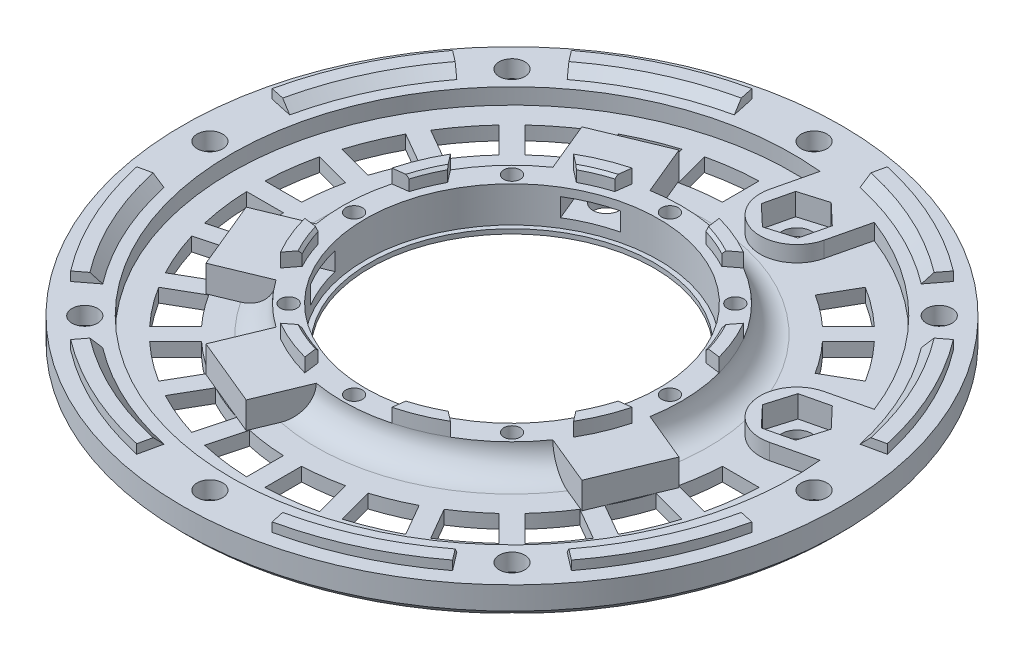
SolidWorks part; units mm, degrees
ref_plane "Front Plane" through (0, 0, 0) normal (0, 0, 1) x (1, 0, 0)
ref_plane "Top Plane" through (0, 0, 0) normal (0, 1, 0) x (1, 0, 0)
ref_plane "Right Plane" through (0, 0, 0) normal (1, 0, 0) x (0, 0, -1)
sketch "Sketch1" plane through (0, 0, 0) normal (0, 1, 0) x (1, 0, 0)
  circle A0 centre (0, 0) radius 16.025
  circle A1 centre (0, 0) radius 36
  dimension "D1" = 32.05
  dimension "D2" = 72
extrude "Boss-Extrude1" add sketch "Sketch1" along normal blind 1
sketch "Sketch2" plane through (0, 0, 0) normal (0, -1, 0) x (1, 0, 0)
  circle A0 centre (0, 0) radius 17.25 construction
  circle A1 centre (0, 0) radius 18.5 construction
  circle A2 centre (0, 0) radius 18.5
  circle A3 centre (0, 0) radius 16.025 construction
  circle A4 centre (0, 0) radius 16.025
  arc A5 (-1.2, 18.461) -> (-4.705, 17.8917) centre (0, 0) ccw construction
  point P3 (0, -17.25)
extrude "Boss-Extrude2" add sketch "Sketch2" against normal offset from surface (3.9 mm away) 3.9 up to face at (0, 0, 36)
fillet "Fillet1" radius 2.9 1 edges at (0, 1, 18.5)
sketch "Sketch4" plane through (0, 0, 0) normal (0, 1, 0) x (1, 0, 0)
  circle A0 centre (0, 0) radius 15.525
  circle A1 centre (0, 0) radius 36
  circle A2 centre (0, 0) radius 36
  circle A3 centre (0, 0) radius 16.025 construction
  dimension "D2" = 0.5
  dimension "D1" = 0
extrude "Boss-Extrude3" add sketch "Sketch4" against normal blind 0.5
sketch "Sketch5" plane through (0, 1, 0) normal (0, 1, 0) x (1, 0, 0)
  line L0 (27.99, -0.75) -> (19.9859, -0.75) construction
  line L1 (19.9859, 0.75) -> (27.99, 0.75) construction
  line L2 (27.99, -0.75) -> (19.9859, -0.75) construction
  line L3 (19.9859, 0.75) -> (27.99, 0.75) construction
  line L4 (0, 0) -> (36, 0) construction
  line L5 (0, 0) -> (34.7733, 9.3175) construction
  line L6 (34.7733, 9.3175) -> (36, 0) construction
  line L7 (0, 0) -> (35.3867, 4.6587) construction
  line L8 (27.99, 1) -> (23.9792, 1)
  line L9 (27.295, 6.2784) -> (23.4209, 5.2403)
  line L10 (27.99, -1) -> (23.9792, -1)
  line L11 (27.295, -6.2784) -> (23.4209, -5.2403)
  line L12 (26.7774, -8.2103) -> (22.9033, -7.1722)
  line L13 (24.74, -13.129) -> (21.2666, -11.1236)
  line L14 (23.74, -14.861) -> (20.2666, -12.8556)
  line L15 (20.499, -19.0848) -> (17.6629, -16.2487)
  line L16 (19.0848, -20.499) -> (16.2487, -17.6629)
  line L17 (14.861, -23.74) -> (12.8556, -20.2666)
  line L18 (13.129, -24.74) -> (11.1236, -21.2666)
  line L19 (8.2103, -26.7774) -> (7.1722, -22.9033)
  line L20 (6.2784, -27.295) -> (5.2403, -23.4209)
  line L21 (1, -27.99) -> (1, -23.9792)
  line L22 (-1, -27.99) -> (-1, -23.9792)
  line L23 (-6.2784, -27.295) -> (-5.2403, -23.4209)
  line L24 (-8.2103, -26.7774) -> (-7.1722, -22.9033)
  line L25 (-13.129, -24.74) -> (-11.1236, -21.2666)
  line L26 (-14.861, -23.74) -> (-12.8556, -20.2666)
  line L27 (-19.0848, -20.499) -> (-16.2487, -17.6629)
  line L28 (-20.499, -19.0848) -> (-17.6629, -16.2487)
  line L29 (-23.74, -14.861) -> (-20.2666, -12.8556)
  line L30 (-24.74, -13.129) -> (-21.2666, -11.1236)
  line L31 (-26.7774, -8.2103) -> (-22.9033, -7.1722)
  line L32 (-27.295, -6.2784) -> (-23.4209, -5.2403)
  line L33 (-27.99, -1) -> (-23.9792, -1)
  line L34 (-27.99, 1) -> (-23.9792, 1)
  line L35 (-27.295, 6.2784) -> (-23.4209, 5.2403)
  line L36 (-26.7774, 8.2103) -> (-22.9033, 7.1722)
  line L37 (-24.74, 13.129) -> (-21.2666, 11.1236)
  line L38 (-23.74, 14.861) -> (-20.2666, 12.8556)
  line L39 (-20.499, 19.0848) -> (-17.6629, 16.2487)
  line L40 (-19.0848, 20.499) -> (-16.2487, 17.6629)
  line L41 (-14.861, 23.74) -> (-12.8556, 20.2666)
  line L42 (-13.129, 24.74) -> (-11.1236, 21.2666)
  line L43 (-8.2103, 26.7774) -> (-7.1722, 22.9033)
  line L44 (-6.2784, 27.295) -> (-5.2403, 23.4209)
  line L45 (-1, 27.99) -> (-1, 23.9792)
  line L46 (1, 27.99) -> (1, 23.9792)
  line L47 (6.2784, 27.295) -> (5.2403, 23.4209)
  line L48 (8.2103, 26.7774) -> (7.1722, 22.9033)
  line L49 (13.129, 24.74) -> (11.1236, 21.2666)
  line L50 (14.861, 23.74) -> (12.8556, 20.2666)
  line L51 (19.0848, 20.499) -> (16.2487, 17.6629)
  line L52 (20.499, 19.0848) -> (17.6629, 16.2487)
  line L53 (23.74, 14.861) -> (20.2666, 12.8556)
  line L54 (24.74, 13.129) -> (21.2666, 11.1236)
  line L55 (26.7774, 8.2103) -> (22.9033, 7.1722)
  line L56 (0, 0) -> (23.9792, 1) construction
  circle A0 centre (0, 0) radius 24 construction
  circle A2 centre (0, 0) radius 36 construction
  arc A3 (23.9792, 1) -> (23.4209, 5.2403) centre (0, 0) ccw
  arc A4 (27.99, 1) -> (27.295, 6.2784) centre (0, 0) ccw
  arc A5 (27.295, -6.2784) -> (27.99, -1) centre (0, 0) ccw
  arc A6 (23.4209, -5.2403) -> (23.9792, -1) centre (0, 0) ccw
  arc A7 (24.74, -13.129) -> (26.7774, -8.2103) centre (0, 0) ccw
  arc A8 (21.2666, -11.1236) -> (22.9033, -7.1722) centre (0, 0) ccw
  arc A9 (20.499, -19.0848) -> (23.74, -14.861) centre (0, 0) ccw
  arc A10 (17.6629, -16.2487) -> (20.2666, -12.8556) centre (0, 0) ccw
  arc A11 (14.861, -23.74) -> (19.0848, -20.499) centre (0, 0) ccw
  arc A12 (12.8556, -20.2666) -> (16.2487, -17.6629) centre (0, 0) ccw
  arc A13 (8.2103, -26.7774) -> (13.129, -24.74) centre (0, 0) ccw
  arc A14 (7.1722, -22.9033) -> (11.1236, -21.2666) centre (0, 0) ccw
  arc A15 (1, -27.99) -> (6.2784, -27.295) centre (0, 0) ccw
  arc A16 (1, -23.9792) -> (5.2403, -23.4209) centre (0, 0) ccw
  arc A17 (-6.2784, -27.295) -> (-1, -27.99) centre (0, 0) ccw
  arc A18 (-5.2403, -23.4209) -> (-1, -23.9792) centre (0, 0) ccw
  arc A19 (-13.129, -24.74) -> (-8.2103, -26.7774) centre (0, 0) ccw
  arc A20 (-11.1236, -21.2666) -> (-7.1722, -22.9033) centre (0, 0) ccw
  arc A21 (-19.0848, -20.499) -> (-14.861, -23.74) centre (0, 0) ccw
  arc A22 (-16.2487, -17.6629) -> (-12.8556, -20.2666) centre (0, 0) ccw
  arc A23 (-23.74, -14.861) -> (-20.499, -19.0848) centre (0, 0) ccw
  arc A24 (-20.2666, -12.8556) -> (-17.6629, -16.2487) centre (0, 0) ccw
  arc A25 (-26.7774, -8.2103) -> (-24.74, -13.129) centre (0, 0) ccw
  arc A26 (-22.9033, -7.1722) -> (-21.2666, -11.1236) centre (0, 0) ccw
  arc A27 (-27.99, -1) -> (-27.295, -6.2784) centre (0, 0) ccw
  arc A28 (-23.9792, -1) -> (-23.4209, -5.2403) centre (0, 0) ccw
  arc A29 (-27.295, 6.2784) -> (-27.99, 1) centre (0, 0) ccw
  arc A30 (-23.4209, 5.2403) -> (-23.9792, 1) centre (0, 0) ccw
  arc A31 (-24.74, 13.129) -> (-26.7774, 8.2103) centre (0, 0) ccw
  arc A32 (-21.2666, 11.1236) -> (-22.9033, 7.1722) centre (0, 0) ccw
  arc A33 (-20.499, 19.0848) -> (-23.74, 14.861) centre (0, 0) ccw
  arc A34 (-17.6629, 16.2487) -> (-20.2666, 12.8556) centre (0, 0) ccw
  arc A35 (-14.861, 23.74) -> (-19.0848, 20.499) centre (0, 0) ccw
  arc A36 (-12.8556, 20.2666) -> (-16.2487, 17.6629) centre (0, 0) ccw
  arc A37 (-8.2103, 26.7774) -> (-13.129, 24.74) centre (0, 0) ccw
  arc A38 (-7.1722, 22.9033) -> (-11.1236, 21.2666) centre (0, 0) ccw
  arc A39 (-1, 27.99) -> (-6.2784, 27.295) centre (0, 0) ccw
  arc A40 (-1, 23.9792) -> (-5.2403, 23.4209) centre (0, 0) ccw
  arc A41 (6.2784, 27.295) -> (1, 27.99) centre (0, 0) ccw
  arc A42 (5.2403, 23.4209) -> (1, 23.9792) centre (0, 0) ccw
  arc A43 (13.129, 24.74) -> (8.2103, 26.7774) centre (0, 0) ccw
  arc A44 (11.1236, 21.2666) -> (7.1722, 22.9033) centre (0, 0) ccw
  arc A45 (19.0848, 20.499) -> (14.861, 23.74) centre (0, 0) ccw
  arc A46 (16.2487, 17.6629) -> (12.8556, 20.2666) centre (0, 0) ccw
  arc A47 (23.74, 14.861) -> (20.499, 19.0848) centre (0, 0) ccw
  arc A48 (20.2666, 12.8556) -> (17.6629, 16.2487) centre (0, 0) ccw
  arc A49 (26.7774, 8.2103) -> (24.74, 13.129) centre (0, 0) ccw
  arc A50 (22.9033, 7.1722) -> (21.2666, 11.1236) centre (0, 0) ccw
  dimension "D1" = 15
  dimension "D2" = 1
  dimension "D4" = 24
  dimension "D3" = 24
extrude "Cut-Extrude1" cut sketch "Sketch5" against normal through all both and the other way through all
sketch "Sketch7" plane through (0, 3.9, 0) normal (0, 1, 0) x (1, 0, 0)
  line L0 (0, 0) -> (0, 17.25) construction
  circle A0 centre (0, 17.25) radius 0.9
  circle A1 centre (12.1976, 12.1976) radius 0.9
  circle A2 centre (17.25, 0) radius 0.9
  circle A3 centre (12.1976, -12.1976) radius 0.9
  circle A4 centre (0, -17.25) radius 0.9
  circle A5 centre (-12.1976, -12.1976) radius 0.9
  circle A6 centre (-17.25, 0) radius 0.9
  circle A7 centre (-12.1976, 12.1976) radius 0.9
  point P21 (0, 0)
  dimension "D1" = 1.8
  dimension "D2" = 8
extrude "Cut-Extrude2" cut sketch "Sketch7" against normal through all
sketch "Sketch8" plane through (0, 1, 0) normal (0, 1, 0) x (1, 0, 0)
  arc A0 (-30.6392, -0.8144) -> (-29.9521, -6.5032) centre (0, 0) ccw construction
  arc A1 (-30.6392, -0.8144) -> (-29.9521, -6.5032) centre (0, 0) ccw construction
  arc A2 (-29.9521, 6.5032) -> (-30.6392, 0.8144) centre (0, 0) ccw construction
  arc A3 (-29.9521, 6.5032) -> (-30.6392, 0.8144) centre (0, 0) ccw construction
  circle A5 centre (0, 0) radius 30.65
  circle A6 centre (0, 0) radius 36 construction
  circle A7 centre (0, 0) radius 36
extrude "Boss-Extrude4" add sketch "Sketch8" along normal blind 1.7378
sketch "Sketch9" plane through (0, 2.7378, 0) normal (0, 1, 0) x (1, 0, 0)
  line L0 (0, 0) -> (-29.9521, 6.5032) construction
  line L1 (0, 0) -> (-29.9521, -6.5032) construction
  line L2 (-29.9521, 6.5032) -> (-29.9521, -6.5032) construction
  line L3 (-27.3707, 21.0023) -> (-23.9196, 18.3542) construction
  line L4 (0, 0) -> (0, 36) construction
  line L5 (0, 0) -> (-25.4558, 25.4558) construction
  line L6 (-24.3163, 18.6585) -> (0, 0) construction
  line L7 (-24.3163, 18.6585) -> (-28.5607, 21.9154) construction
  line L8 (-29.9521, 6.5032) -> (-35.1803, 7.6384) construction
  line L9 (-27.3521, 20.862) -> (-25.3687, 19.3401)
  line L10 (-31.2086, 14.47) -> (0, 0) construction
  line L11 (-33.5954, 7.3966) -> (-31.1523, 6.8662)
  line L12 (-7.3966, 33.5954) -> (-6.8662, 31.1523)
  line L13 (-20.862, 27.3521) -> (-19.3401, 25.3687)
  arc A0 (-29.9521, 6.5032) -> (-24.3163, 18.6585) centre (0, 0) cw construction
  arc A1 (-35.1803, 7.6384) -> (-28.5607, 21.9154) centre (0, 0) cw construction
  circle A2 centre (0, 0) radius 36 construction
  circle A3 centre (0, 0) radius 30.65 construction
  arc A4 (-27.2914, 20.9414) -> (-33.6168, 7.2989) centre (0, 0) ccw construction
  arc A5 (-31.1523, 6.8662) -> (-25.3687, 19.3401) centre (0, 0) cw
  arc A6 (-33.5954, 7.3966) -> (-27.3521, 20.862) centre (0, 0) cw
  circle A7 centre (0, 0) radius 36 construction
  arc A8 (-6.8662, 31.1523) -> (-19.3401, 25.3687) centre (0, 0) ccw
  arc A9 (-7.3966, 33.5954) -> (-20.862, 27.3521) centre (0, 0) ccw
  dimension "D2" = 0.1
  dimension "D3" = 45
  dimension "D4" = 0.1
  dimension "D1" = 2.5
extrude "Boss-Extrude5" add sketch "Sketch9" along normal blind 1
ref_axis "Axis1" through (0, -0.72, 0) along (0, 1, 0)
pattern_circular "CirPattern1" count 4 over 360 about axis through (0, -0.72, 0) along (0, 1, 0) of "Boss-Extrude5"
chamfer "Chamfer1" distance 1 angle 45 8 edges at (-28.9406, 3.7378, -13.4184) (-13.4184, 3.7378, -28.9406) (13.4184, 3.7378, -28.9406) (28.9406, 3.7378, -13.4184) (28.9406, 3.7378, 13.4184) (13.4184, 3.7378, 28.9406) (-13.4184, 3.7378, 28.9406) (-28.9406, 3.7378, 13.4184)
sketch "Sketch10" plane through (0, 2.7378, 0) normal (0, 1, 0) x (1, 0, 0)
  line L0 (0, 0) -> (0, 36) construction
  circle A0 centre (0, 0) radius 36 construction
  circle A1 centre (0, 33) radius 1.4 construction
  circle A2 centre (0, 33) radius 1.4
  circle A3 centre (23.3345, 23.3345) radius 1.4
  circle A4 centre (33, 0) radius 1.4
  circle A5 centre (23.3345, -23.3345) radius 1.4
  circle A6 centre (0, -33) radius 1.4
  circle A7 centre (-23.3345, -23.3345) radius 1.4
  circle A8 centre (-33, 0) radius 1.4
  circle A9 centre (-23.3345, 23.3345) radius 1.4
  point P26 (0, 0)
  dimension "D1" = 8
extrude "Cut-Extrude3" cut sketch "Sketch10" against normal through all both and the other way through all
chamfer "Chamfer2" distance 0.75 angle 45 1 edges at (0, -0.5, 36)
hole_wizard "CSK for M2.5 Flat Head Machine Screw1" positions "Sketch11" profile "Sketch12" countersink size "M2.5" standard "ANSI Metric" end condition through all
sketch "Sketch11" plane through (0, -0.5, 0) normal (0, -1, 0) x (-1, 0, 0)
  point P0 (0, -33)
  point P3 (23.3345, -23.3345)
  point P6 (33, 0)
  point P9 (23.3345, 23.3345)
  point P12 (0, 33)
  point P15 (-23.3345, 23.3345)
  point P18 (-33, 0)
  point P21 (-23.3345, -23.3345)
sketch "Sketch12" plane through (0, -0.5, 33) normal (1, 0, 0) x (0, 0, -1)
  line L0 (0, 0) -> (0, 4.4)
  line L1 (0, 4.4) -> (1.35, 4.4)
  line L2 (1.35, 4.4) -> (1.35, 1.4)
  line L3 (1.35, 1.4) -> (2.75, 0)
  line L5 (2.75, 0) -> (0, 0)
  line L6 (-1.35, 1.4) -> (-2.75, 0) construction
  line L11 (0, -6.35) -> (0, 107.95) construction
  dimension "Thru Hole Dia." = 2.7
  dimension "Thru Hole Depth" = 4.4
  dimension "Near C'Sink Dia." = 5.5
  dimension "Near C'Sink Angle" = 90
sketch "Sketch13" plane through (0, 3.9, 0) normal (0, 1, 0) x (1, 0, 0)
  line L0 (0, 0) -> (-7.0796, 17.0918) construction
  line L1 (0, 0) -> (0, 18.5) construction
  line L2 (-9.2808, 16.0037) -> (-7.9403, 14.9751)
  line L3 (-4.7538, 17.8788) -> (-4.9743, 16.2037)
  line L4 (4.7538, 17.8788) -> (4.9743, 16.2037)
  line L5 (9.2808, 16.0037) -> (7.9403, 14.9751)
  line L6 (16.0037, 9.2808) -> (14.9751, 7.9403)
  line L7 (17.8788, 4.7538) -> (16.2037, 4.9743)
  line L8 (17.8788, -4.7538) -> (16.2037, -4.9743)
  line L9 (16.0037, -9.2808) -> (14.9751, -7.9403)
  line L10 (9.2808, -16.0037) -> (7.9403, -14.9751)
  line L11 (4.7538, -17.8788) -> (4.9743, -16.2037)
  line L12 (-4.7538, -17.8788) -> (-4.9743, -16.2037)
  line L13 (-9.2808, -16.0037) -> (-7.9403, -14.9751)
  line L14 (-16.0037, -9.2808) -> (-14.9751, -7.9403)
  line L15 (-17.8788, -4.7538) -> (-16.2037, -4.9743)
  line L16 (-17.8788, 4.7538) -> (-16.2037, 4.9743)
  line L17 (-16.0037, 9.2808) -> (-14.9751, 7.9403)
  circle A0 centre (0, 0) radius 18.5 construction
  arc A1 (-7.9403, 14.9751) -> (-4.9743, 16.2037) centre (0, 0) cw
  arc A2 (-9.2808, 16.0037) -> (-4.7538, 17.8788) centre (0, 0) cw
  arc A3 (4.9743, 16.2037) -> (7.9403, 14.9751) centre (0, 0) cw
  arc A4 (4.7538, 17.8788) -> (9.2808, 16.0037) centre (0, 0) cw
  arc A5 (14.9751, 7.9403) -> (16.2037, 4.9743) centre (0, 0) cw
  arc A6 (16.0037, 9.2808) -> (17.8788, 4.7538) centre (0, 0) cw
  arc A7 (16.2037, -4.9743) -> (14.9751, -7.9403) centre (0, 0) cw
  arc A8 (17.8788, -4.7538) -> (16.0037, -9.2808) centre (0, 0) cw
  arc A9 (7.9403, -14.9751) -> (4.9743, -16.2037) centre (0, 0) cw
  arc A10 (9.2808, -16.0037) -> (4.7538, -17.8788) centre (0, 0) cw
  arc A11 (-4.9743, -16.2037) -> (-7.9403, -14.9751) centre (0, 0) cw
  arc A12 (-4.7538, -17.8788) -> (-9.2808, -16.0037) centre (0, 0) cw
  arc A13 (-14.9751, -7.9403) -> (-16.2037, -4.9743) centre (0, 0) cw
  arc A14 (-16.0037, -9.2808) -> (-17.8788, -4.7538) centre (0, 0) cw
  arc A15 (-16.2037, 4.9743) -> (-14.9751, 7.9403) centre (0, 0) cw
  arc A16 (-17.8788, 4.7538) -> (-16.0037, 9.2808) centre (0, 0) cw
  point P12 (-6.4865, 15.6598)
  point P20 (6.4865, 15.6598)
  point P25 (15.6598, 6.4865)
  point P30 (15.6598, -6.4865)
  point P35 (6.4865, -15.6598)
  point P40 (-6.4865, -15.6598)
  point P45 (-15.6598, -6.4865)
  point P50 (-15.6598, 6.4865)
  point P51 (0, 0)
  dimension "D1" = 22.5
  dimension "D2" = 30
  dimension "D3" = 1.55
  dimension "D4" = 4.9
  dimension "D5" = 8
extrude "Boss-Extrude6" add sketch "Sketch13" along normal blind 1.5
chamfer "Chamfer3" distance 0.3 angle 45 8 edges at (-15.6598, 5.4, -6.4865) (-15.6598, 5.4, 6.4865) (-6.4865, 5.4, 15.6598) (6.4865, 5.4, 15.6598) (15.6598, 5.4, 6.4865) (15.6598, 5.4, -6.4865) (6.4865, 5.4, -15.6598) (-6.4865, 5.4, -15.6598)
sketch "Sketch14" plane through (0, -0.5, 0) normal (0, -1, 0) x (1, 0, 0)
  line L0 (0, 0) -> (25.4558, -25.4558) construction
  line L1 (0, 0) -> (0, -36) construction
  line L6 (0, 0) -> (-22.1731, 9.1844) construction
  line L7 (0, 0) -> (-9.1844, -22.1731) construction
  circle A0 centre (0, 0) radius 36 construction
  circle A1 centre (0, 0) radius 16.025 construction
  arc A5 (-21.2666, 11.1236) -> (-22.9033, 7.1722) centre (0, 0) ccw construction
  circle A6 centre (-17.5768, 7.2806) radius 1.45
  circle A7 centre (-17.5768, 7.2806) radius 4.975 construction
  arc A8 (-11.1236, -21.2666) -> (-7.1722, -22.9033) centre (0, 0) ccw construction
  circle A9 centre (-7.2806, -17.5768) radius 1.45
  circle A10 centre (-7.2806, -17.5768) radius 4.975 construction
  circle A11 centre (17.5768, 7.2806) radius 1.45
  circle A12 centre (-7.2806, 17.5768) radius 1.45
  point P25 (-14.8052, 6.1325)
  point P28 (-16.2372, 6.7257)
  dimension "D2" = 2.9
  dimension "D3" = 3
  dimension "D1" = 45
sketch "Sketch15" plane through (0, 1, 0) normal (0, 1, 0) x (1, 0, 0)
  line L0 (-9.8825, 13.2519) -> (-12.8979, 20.5316)
  line L1 (-9.8825, 13.2519) -> (-2.3825, 16.3585)
  line L2 (-12.8979, 20.5316) -> (-5.3979, 23.6382)
  line L3 (-2.3825, 16.3585) -> (-5.3979, 23.6382)
  line L4 (-9.8825, 13.2519) -> (-5.3979, 23.6382) construction
  line L5 (-12.8979, 20.5316) -> (-2.3825, 16.3585) construction
  line L6 (0, 0) -> (-9.1844, 22.1731) construction
  line L7 (2.3825, 16.3585) -> (5.3979, 23.6382) [skipped]
  line L8 (2.3825, 16.3585) -> (9.8825, 13.2519) [skipped]
  line L9 (5.3979, 23.6382) -> (12.8979, 20.5316) [skipped]
  line L10 (9.8825, 13.2519) -> (12.8979, 20.5316) [skipped]
  line L11 (2.3825, 16.3585) -> (12.8979, 20.5316) construction
  line L12 (5.3979, 23.6382) -> (9.8825, 13.2519) construction
  line L13 (13.2519, 9.8825) -> (20.5316, 12.8979) [skipped]
  line L14 (13.2519, 9.8825) -> (16.3585, 2.3825) [skipped]
  line L15 (20.5316, 12.8979) -> (23.6382, 5.3979) [skipped]
  line L16 (16.3585, 2.3825) -> (23.6382, 5.3979) [skipped]
  line L17 (13.2519, 9.8825) -> (23.6382, 5.3979) construction
  line L18 (20.5316, 12.8979) -> (16.3585, 2.3825) construction
  line L19 (16.3585, -2.3825) -> (23.6382, -5.3979)
  line L20 (16.3585, -2.3825) -> (13.2519, -9.8825)
  line L21 (23.6382, -5.3979) -> (20.5316, -12.8979)
  line L22 (13.2519, -9.8825) -> (20.5316, -12.8979)
  line L23 (16.3585, -2.3825) -> (20.5316, -12.8979) construction
  line L24 (23.6382, -5.3979) -> (13.2519, -9.8825) construction
  line L25 (9.8825, -13.2519) -> (12.8979, -20.5316) [skipped]
  line L26 (9.8825, -13.2519) -> (2.3825, -16.3585) [skipped]
  line L27 (12.8979, -20.5316) -> (5.3979, -23.6382) [skipped]
  line L28 (2.3825, -16.3585) -> (5.3979, -23.6382) [skipped]
  line L29 (9.8825, -13.2519) -> (5.3979, -23.6382) construction
  line L30 (12.8979, -20.5316) -> (2.3825, -16.3585) construction
  line L31 (-2.3825, -16.3585) -> (-5.3979, -23.6382)
  line L32 (-2.3825, -16.3585) -> (-9.8825, -13.2519)
  line L33 (-5.3979, -23.6382) -> (-12.8979, -20.5316)
  line L34 (-9.8825, -13.2519) -> (-12.8979, -20.5316)
  line L35 (-2.3825, -16.3585) -> (-12.8979, -20.5316) construction
  line L36 (-5.3979, -23.6382) -> (-9.8825, -13.2519) construction
  line L37 (-13.2519, -9.8825) -> (-20.5316, -12.8979)
  line L38 (-13.2519, -9.8825) -> (-16.3585, -2.3825)
  line L39 (-20.5316, -12.8979) -> (-23.6382, -5.3979)
  line L40 (-16.3585, -2.3825) -> (-23.6382, -5.3979)
  line L41 (-13.2519, -9.8825) -> (-23.6382, -5.3979) construction
  line L42 (-20.5316, -12.8979) -> (-16.3585, -2.3825) construction
  line L43 (-16.3585, 2.3825) -> (-23.6382, 5.3979) [skipped]
  line L44 (-16.3585, 2.3825) -> (-13.2519, 9.8825) [skipped]
  line L45 (-23.6382, 5.3979) -> (-20.5316, 12.8979) [skipped]
  line L46 (-13.2519, 9.8825) -> (-20.5316, 12.8979) [skipped]
  line L47 (-16.3585, 2.3825) -> (-20.5316, 12.8979) construction
  line L48 (-23.6382, 5.3979) -> (-13.2519, 9.8825) construction
  line L49 (0, 0) -> (-9.1844, 22.1731) construction
  arc A1 (-7.1722, 22.9033) -> (-11.1236, 21.2666) centre (0, 0) ccw construction
  circle A2 centre (0, 0) radius 16.025 construction
  point P1 (-7.6402, 18.445)
  point P9 (7.6402, 18.445)
  point P18 (18.445, 7.6402)
  point P23 (18.445, -7.6402)
  point P28 (7.6402, -18.445)
  point P33 (-7.6402, -18.445)
  point P38 (-18.445, -7.6402)
  point P43 (-18.445, 7.6402)
  point P48 (0, 0)
  dimension "D1" = 7.5
  dimension "D2" = 8
extrude "Boss-Extrude7" add sketch "Sketch15" along normal up to surface (2.9 mm away) up to face at (0, 3.9, -16.35)
extrude "Cut-Extrude4" cut sketch "Sketch14" against normal blind 3.5
sketch "Sketch16" plane through (0, -0.5, 0) normal (0, -1, 0) x (1, 0, 0)
  line L0 (0, 0) -> (23.3345, -23.3345) construction
  line L1 (10.1026, 7.7782) -> (22.348, -8.1266) construction
  line L2 (0, 0) -> (0, -17.25) construction
  line L3 (0, 0) -> (10.1026, 7.7782) construction
  line L4 (18.6021, 8.3059) -> (13.454, 13.454) construction
  line L5 (0, 0) -> (13.454, 13.454) construction
  line L6 (25.1212, -5.9915) -> (27.5961, -3.5166) construction
  line L7 (27.5961, -3.5166) -> (12.0398, 12.0398) construction
  circle A0 centre (0, 0) radius 12.75 construction
  circle A1 centre (25.1212, -5.9915) radius 1.65
  circle A2 centre (25.1212, -5.9915) radius 3.5 construction
  circle A3 centre (17.5768, 7.2806) radius 1.45 construction
  circle A4 centre (5.9915, -25.1212) radius 1.65
  dimension "D1" = 25.5
  dimension "D2" = 3.3
  dimension "D3" = 7
  dimension "D4" = 2
  dimension "D5" = 22
sketch "Sketch17" plane through (0, -0.5, 0) normal (0, -1, 0) x (1, 0, 0)
  line L0 (24.74, -13.129) -> (21.2666, -11.1236) construction
  line L1 (24.74, -13.129) -> (21.2666, -11.1236)
  line L2 (0, 0) -> (12.1976, -12.1976) construction
  line L3 (13.129, -24.74) -> (11.1236, -21.2666)
  arc A0 (21.2666, -11.1236) -> (22.9033, -7.1722) centre (0, 0) ccw construction
  arc A1 (24.74, -13.129) -> (26.7774, -8.2103) centre (0, 0) ccw construction
  arc A4 (21.2666, -11.1236) -> (21.5701, -10.5228) centre (0, 0) ccw
  arc A5 (24.74, -13.129) -> (25.4284, -11.7403) centre (0, 0) ccw
  arc A8 (25.4284, -11.7403) -> (21.5701, -10.5228) centre (25.1212, -5.9915) ccw
  arc A9 (11.7403, -25.4284) -> (10.5228, -21.5701) centre (5.9915, -25.1212) cw
  arc A10 (13.129, -24.74) -> (11.7403, -25.4284) centre (0, 0) cw
  arc A11 (11.1236, -21.2666) -> (10.5228, -21.5701) centre (0, 0) cw
extrude "Boss-Extrude8" add sketch "Sketch17" against normal up to surface (1.5 mm away) up to face at (25.7264, 1, -3.3869)
sketch "Sketch18" plane through (0, 1, 0) normal (0, 1, 0) x (1, 0, 0)
  line L0 (0, 0) -> (25.1212, 5.9915) construction
  line L1 (24.1933, 9.8823) -> (28.6308, 10.9407)
  line L2 (26.0492, 2.1006) -> (30.4868, 3.1589)
  line L3 (0, 0) -> (23.3345, 23.3345) construction
  line L4 (9.8823, 24.1933) -> (10.9407, 28.6308)
  line L5 (2.1006, 26.0492) -> (3.1589, 30.4868)
  arc A0 (24.1933, 9.8823) -> (26.0492, 2.1006) centre (25.1212, 5.9915) ccw
  circle A1 centre (0, 0) radius 30.65 construction
  circle A2 centre (0, 0) radius 30.65 construction
  arc A3 (30.4868, 3.1589) -> (28.6308, 10.9407) centre (0, 0) ccw
  arc A4 (3.1589, 30.4868) -> (10.9407, 28.6308) centre (0, 0) cw
  arc A5 (9.8823, 24.1933) -> (2.1006, 26.0492) centre (5.9915, 25.1212) cw
  dimension "D1" = 8
extrude "Boss-Extrude9" add sketch "Sketch18" along normal up to surface (1.7378 mm away) up to face at (0, 2.7378, -31.6)
extrude "Cut-Extrude5" cut sketch "Sketch16" against normal through all
sketch "Sketch19" plane through (0, 2.7378, 0) normal (0, 1, 0) x (1, 0, 0)
  line L0 (0, 0) -> (25.1212, 5.9915) construction
  line L1 (28.1539, 6.7147) -> (26.0112, 8.9794)
  line L2 (26.0112, 8.9794) -> (22.9785, 8.2561)
  line L3 (22.9785, 8.2561) -> (22.0886, 5.2682)
  line L4 (22.0886, 5.2682) -> (24.2313, 3.0035)
  line L5 (24.2313, 3.0035) -> (27.2639, 3.7268)
  line L6 (27.2639, 3.7268) -> (28.1539, 6.7147)
  line L7 (0, 0) -> (23.3345, 23.3345) construction
  line L8 (3.7268, 27.2639) -> (6.7147, 28.1539)
  line L9 (3.0035, 24.2313) -> (3.7268, 27.2639)
  line L10 (5.2682, 22.0886) -> (3.0035, 24.2313)
  line L11 (8.2561, 22.9785) -> (5.2682, 22.0886)
  line L12 (8.9794, 26.0112) -> (8.2561, 22.9785)
  line L13 (6.7147, 28.1539) -> (8.9794, 26.0112)
  circle A0 centre (25.1212, 5.9915) radius 2.7 construction
  dimension "D1" = 5.4
extrude "Cut-Extrude6" cut sketch "Sketch19" against normal blind 2.4
sketch "Sketch20" plane through (0, 3, 0) normal (0, -1, 0) x (1, 0, 0)
  line L0 (0, 0) -> (-17.5768, 7.2806) construction
  line L5 (-15.2866, 9.0379) -> (-13.6672, 8.3671)
  line L6 (-14.9098, 6.1758) -> (-15.2866, 9.0379) construction
  line L16 (-15.2866, 9.0379) -> (-17.9536, 10.1426)
  line L17 (-17.9536, 10.1426) -> (-20.2438, 8.3853)
  line L18 (-20.2438, 8.3853) -> (-19.867, 5.5232)
  line L19 (-19.867, 5.5232) -> (-17.2, 4.4185)
  line L20 (-17.2, 4.4185) -> (-14.9098, 6.1758) construction
  line L21 (-13.6672, 8.3671) -> (-15.5806, 3.7477)
  line L28 (-15.5806, 3.7477) -> (-17.2, 4.4185)
  line L29 (-8.3671, 13.6672) -> (-9.0379, 15.2866)
  line L30 (-10.1426, 17.9536) -> (-9.0379, 15.2866)
  line L31 (-8.3853, 20.2438) -> (-10.1426, 17.9536)
  line L32 (-5.5232, 19.867) -> (-8.3853, 20.2438)
  line L33 (-4.4185, 17.2) -> (-5.5232, 19.867)
  line L34 (-4.4185, 17.2) -> (-3.7477, 15.5806)
  line L35 (-3.7477, 15.5806) -> (-8.3671, 13.6672)
  line L36 (3.7477, 15.5806) -> (4.4185, 17.2) [skipped]
  line L37 (5.5232, 19.867) -> (4.4185, 17.2) [skipped]
  line L38 (8.3853, 20.2438) -> (5.5232, 19.867) [skipped]
  line L39 (10.1426, 17.9536) -> (8.3853, 20.2438) [skipped]
  line L46 (9.0379, 15.2866) -> (10.1426, 17.9536) [skipped]
  line L47 (9.0379, 15.2866) -> (8.3671, 13.6672) [skipped]
  line L48 (8.3671, 13.6672) -> (3.7477, 15.5806) [skipped]
  line L49 (13.6672, 8.3671) -> (15.2866, 9.0379)
  line L50 (17.9536, 10.1426) -> (15.2866, 9.0379)
  line L51 (20.2438, 8.3853) -> (17.9536, 10.1426)
  line L52 (19.867, 5.5232) -> (20.2438, 8.3853)
  line L53 (17.2, 4.4185) -> (19.867, 5.5232)
  line L54 (17.2, 4.4185) -> (15.5806, 3.7477)
  line L55 (15.5806, 3.7477) -> (13.6672, 8.3671)
  line L56 (15.5806, -3.7477) -> (17.2, -4.4185) [skipped]
  line L57 (19.867, -5.5232) -> (17.2, -4.4185) [skipped]
  line L58 (20.2438, -8.3853) -> (19.867, -5.5232) [skipped]
  line L59 (17.9536, -10.1426) -> (20.2438, -8.3853) [skipped]
  line L60 (15.2866, -9.0379) -> (17.9536, -10.1426) [skipped]
  line L61 (15.2866, -9.0379) -> (13.6672, -8.3671) [skipped]
  line L62 (13.6672, -8.3671) -> (15.5806, -3.7477) [skipped]
  line L63 (8.3671, -13.6672) -> (9.0379, -15.2866) [skipped]
  line L64 (10.1426, -17.9536) -> (9.0379, -15.2866) [skipped]
  line L65 (8.3853, -20.2438) -> (10.1426, -17.9536) [skipped]
  line L66 (5.5232, -19.867) -> (8.3853, -20.2438) [skipped]
  line L67 (4.4185, -17.2) -> (5.5232, -19.867) [skipped]
  line L68 (4.4185, -17.2) -> (3.7477, -15.5806) [skipped]
  line L69 (3.7477, -15.5806) -> (8.3671, -13.6672) [skipped]
  line L70 (-3.7477, -15.5806) -> (-4.4185, -17.2)
  line L71 (-5.5232, -19.867) -> (-4.4185, -17.2)
  line L72 (-8.3853, -20.2438) -> (-5.5232, -19.867)
  line L73 (-10.1426, -17.9536) -> (-8.3853, -20.2438)
  line L74 (-9.0379, -15.2866) -> (-10.1426, -17.9536)
  line L75 (-9.0379, -15.2866) -> (-8.3671, -13.6672)
  line L76 (-8.3671, -13.6672) -> (-3.7477, -15.5806)
  line L77 (-13.6672, -8.3671) -> (-15.2866, -9.0379) [skipped]
  line L78 (-17.9536, -10.1426) -> (-15.2866, -9.0379) [skipped]
  line L79 (-20.2438, -8.3853) -> (-17.9536, -10.1426) [skipped]
  line L80 (-19.867, -5.5232) -> (-20.2438, -8.3853) [skipped]
  line L81 (-17.2, -4.4185) -> (-19.867, -5.5232) [skipped]
  line L82 (-17.2, -4.4185) -> (-15.5806, -3.7477) [skipped]
  line L83 (-15.5806, -3.7477) -> (-13.6672, -8.3671) [skipped]
  circle A1 centre (-17.5768, 7.2806) radius 2.5 construction
  circle A3 centre (0, 0) radius 16.025 construction
  point P57 (0, 0)
  point P69 (0, 0)
  dimension "D1" = 5
extrude "Cut-Extrude7" cut sketch "Sketch20" along normal blind 2
ref_plane "Plane1" through (0.6364, 0, 0.6364) normal (-0.7071, 0, -0.7071) x (-0.7071, 0, 0.7071)
